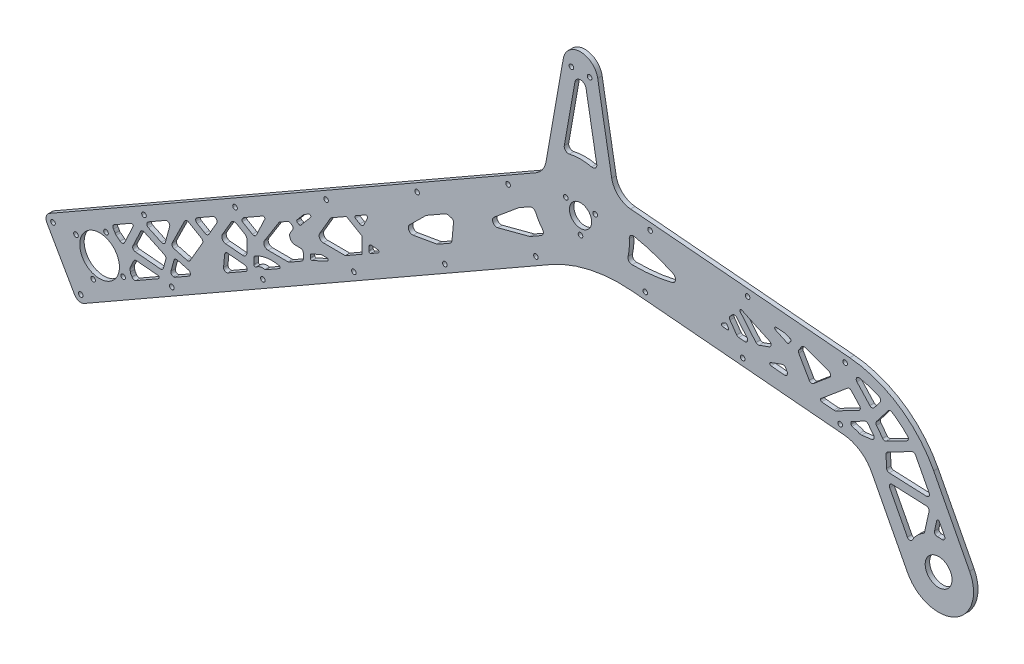
SolidWorks part; units mm, degrees
material "6061-T6 (SS)"
ref_plane "Front Plane" through (0, 0, 0) normal (0, 0, 1) x (1, 0, 0)
ref_plane "Top Plane" through (0, 0, 0) normal (0, 1, 0) x (1, 0, 0)
ref_plane "Right Plane" through (0, 0, 0) normal (1, 0, 0) x (0, 0, -1)
sketch "Reference Sketch" plane through (0, 0, 0) normal (0, 0, 1) x (1, 0, 0)
  line L0 (-343.92, -196.825) -> (0, 0) construction
  line L1 (-243.92, 103.175) -> (356.08, 103.175) construction
  line L2 (-243.92, 103.175) -> (-243.92, 0) construction
  line L3 (-243.92, 0) -> (356.08, 0) construction
  line L4 (356.08, 103.175) -> (356.08, 0) construction
  line L5 (0, 0) -> (256.08, -92.7116) construction
  line L6 (256.08, -92.7116) -> (56.08, -196.825) construction
  line L7 (256.08, -92.7116) -> (456.08, -196.825) construction
  line L8 (-343.92, -196.825) -> (56.08, -196.825) construction
  line L9 (56.08, -196.825) -> (456.08, -196.825) construction
  circle A1 centre (-343.92, -196.825) radius 100 construction
  circle A2 centre (56.08, -196.825) radius 100 construction
  circle A3 centre (456.08, -196.825) radius 100 construction
  circle A4 centre (-343.92, -196.825) radius 16.05 construction
  circle A5 centre (-343.92, -196.825) radius 28.55 construction
  circle A6 centre (-343.92, -196.825) radius 38.55 construction
  circle A7 centre (-343.92, -196.825) radius 33.55 construction
  point P13 (-343.92, -296.825)
  point P14 (556.08, -196.825)
  point P17 (-443.92, -196.825)
  dimension "D3" = 32.1
  dimension "D5" = 200
  dimension "D9" = 57.1
  dimension "D10" = 10
  dimension "D11" = 5
  dimension "D1" = 600
  dimension "D2" = 103.175
  dimension "D4" = 243.92
  dimension "D6" = 125
  dimension "D7" = 400
  dimension "D8" = 1000
  dimension "D12" = 356.08
sketch "Sketch2" plane through (0, 0, 0) normal (0, 0, 1) x (1, 0, 0)
  line L0 (-379.7168, -188.5069) -> (-32.0065, 10.4873)
  line L1 (-354.8814, -231.9028) -> (-21.5627, -41.1449)
  line L2 (-343.92, -196.825) -> (0, 0) construction
  line L3 (-184.3777, -76.7146) -> (-159.5423, -120.1104) construction
  line L4 (-24.685, 20.9013) -> (-12.3101, 91.0831)
  line L5 (12.3101, 91.0831) -> (22.322, 34.3028)
  line L6 (0, 98.4125) -> (0, 112.7) construction
  line L7 (-5.4848, 79.4125) -> (5.4848, 79.4125) construction
  line L8 (5.4848, 79.4125) -> (10.9697, 88.9125) construction
  line L9 (10.9697, 88.9125) -> (5.4848, 98.4125) construction
  line L10 (5.4848, 98.4125) -> (-5.4848, 98.4125) construction
  line L11 (-5.4848, 98.4125) -> (-10.9697, 88.9125) construction
  line L12 (-10.9697, 88.9125) -> (-5.4848, 79.4125) construction
  line L13 (-243.92, 103.175) -> (356.08, 103.175) construction
  line L14 (0, 88.9125) -> (0, 0) construction
  line L15 (35.7868, 21.9646) -> (192.5861, 8.2464)
  line L16 (252.5753, -31.8371) -> (278.2553, -81.1679)
  line L17 (233.9047, -104.2553) -> (208.2247, -54.9245)
  line L18 (36.8237, -28.3172) -> (188.2284, -41.5633)
  line L19 (0, 0) -> (192.5861, -16.8491) construction
  line L21 (-360.8064, -192.2315) -> (-339.3265, -179.9386) construction
  line L22 (-381.5729, -195.33) -> (-361.7045, -230.0467)
  line L23 (256.08, -92.7116) -> (56.08, -196.825) construction
  line L25 (-243.92, 0) -> (356.08, 0) construction
  circle A0 centre (0, 0) radius 7.9375
  circle A1 centre (-343.92, -196.825) radius 14.2
  arc A3 (-12.3101, 91.0831) -> (12.3101, 91.0831) centre (0, 88.9125) cw
  circle A4 centre (0, 88.9125) radius 6.5 construction
  circle A5 centre (-6.5, 88.9125) radius 1.65
  circle A6 centre (6.5, 88.9125) radius 1.65
  circle A7 centre (0, 88.9125) radius 9.5 construction
  arc A8 (252.5753, -31.8371) -> (192.5861, 8.2464) centre (186.0495, -66.4682) ccw
  circle A9 centre (256.08, -92.7116) radius 9.5885
  arc A10 (278.2553, -81.1679) -> (233.9047, -104.2553) centre (256.08, -92.7116) cw
  arc A11 (-21.5627, -41.1449) -> (36.8237, -28.3172) centre (28.1082, -127.9366) cw
  arc A12 (188.2284, -41.5633) -> (208.2247, -54.9245) centre (186.0495, -66.4682) cw
  arc A13 (22.322, 34.3028) -> (35.7868, 21.9646) centre (37.0941, 36.9075) ccw
  arc A14 (-32.0065, 10.4873) -> (-24.685, 20.9013) centre (-39.4572, 23.506) ccw
  circle A17 centre (-343.92, -196.825) radius 17.5 construction
  circle A18 centre (-360.8064, -192.2315) radius 1.65
  circle A19 centre (-339.3265, -179.9386) radius 1.65
  circle A20 centre (-327.0336, -201.4185) radius 1.65
  circle A21 centre (-348.5135, -213.7114) radius 1.65
  arc A27 (-379.7168, -188.5069) -> (-381.5729, -195.33) centre (-377.2333, -192.8465) ccw
  arc A28 (-361.7045, -230.0467) -> (-354.8814, -231.9028) centre (-357.3649, -227.5632) ccw
  circle A29 centre (-343.92, -196.825) radius 33.55 construction
  circle A32 centre (-343.92, -196.825) radius 38.55 construction
  point P16 (-171.96, -98.4125)
  point P64 (-343.92, -196.825)
  dimension "D1" = 15.875
  dimension "D2" = 28.4
  dimension "D3" = 35
  dimension "D5" = 13
  dimension "D6" = 3.3
  dimension "D7" = 6
  dimension "D12" = 50
  dimension "D14" = 100
  dimension "D16" = 15
  dimension "D17" = 5
  dimension "D18" = 25
  dimension "D19" = 3.3
  dimension "D15" = 4
  dimension "D20" = 19.177
  dimension "D4" = 50
  dimension "D8" = 19
  dimension "D9" = 14.2875
  dimension "D10" = 9.525
  dimension "D11" = 10
  dimension "D13" = 50
extrude "Base" add sketch "Sketch2" along normal blind 3.175
sketch "Sketch3" plane through (0, 0, 3.175) normal (0, 0, 1) x (1, 0, 0)
  line L0 (-343.92, -196.825) -> (0, 0) construction
  line L5 (0, 0) -> (197.3986, -17.2701) construction
  line L6 (192.5861, 8.2464) -> (35.7868, 21.9646) construction
  line L9 (36.8237, -28.3172) -> (188.2284, -41.5633) construction
  line L10 (-31.8958, -41.2976) -> (0, 0) construction
  line L11 (0, 0) -> (46.2693, -24.1244) construction
  circle A0 centre (-357.3649, -227.5632) radius 1.65
  circle A1 centre (-343.92, -196.825) radius 33.55 construction
  arc A2 (-361.7045, -230.0467) -> (-354.8814, -231.9028) centre (-357.3649, -227.5632) ccw construction
  circle A3 centre (-292.2711, -190.3101) radius 1.65
  circle A4 centre (-227.1773, -153.057) radius 1.65
  circle A5 centre (-162.0835, -115.8038) radius 1.65
  circle A6 centre (-96.9897, -78.5507) radius 1.65
  circle A7 centre (-31.8958, -41.2976) radius 1.65
  circle A8 centre (-312.1394, -155.5934) radius 1.65
  circle A9 centre (-377.2333, -192.8465) radius 1.65
  circle A10 centre (-247.0456, -118.3403) radius 1.65
  circle A11 centre (-181.9518, -81.0871) radius 1.65
  circle A12 centre (-116.858, -43.834) radius 1.65
  circle A13 centre (-51.7642, -6.5809) radius 1.65
  circle A14 centre (46.2693, -24.1244) radius 1.65
  circle A15 centre (116.0029, -30.2253) radius 1.65
  circle A16 centre (185.7366, -36.3262) radius 1.65
  circle A17 centre (189.2228, 3.5215) radius 1.65
  circle A18 centre (119.4892, 9.6224) radius 1.65
  circle A19 centre (49.7555, 15.7234) radius 1.65
  dimension "D1" = 3.3
  dimension "D2" = 6
  dimension "D3" = 5
  dimension "D5" = 3
  dimension "D4" = 75
  dimension "D6" = 70
extrude "Strut Holes" cut sketch "Sketch3" against normal through all
sketch "Sketch6" plane through (0, 0, 3.175) normal (0, 0, 1) x (1, 0, 0)
  line L0 (-317.9371, -199.2378) -> (-301.7593, -189.9792)
  line L1 (-354.8814, -231.9028) -> (-21.5627, -41.1449) construction
  line L2 (-289.845, -183.1607) -> (-279.9388, -177.4914)
  line L3 (-225.0683, -146.089) -> (-215.3943, -140.5526)
  line L4 (-202.4502, -105.5293) -> (-201.3111, -106.1928)
  line L5 (-333.4446, -172.395) -> (-321.3247, -165.4588)
  line L6 (-32.0065, 10.4873) -> (-379.7168, -188.5069) construction
  line L7 (-319.9233, -166.7528) -> (-326.0767, -179.819)
  line L8 (-329.2222, -183.6702) -> (-327.9453, -183.7868) construction
  line L9 (-302.165, -188.1154) -> (-317.5291, -186.7124)
  line L10 (-319.5204, -187.852) -> (-321.9207, -192.9489)
  line L11 (-296.5261, -175.2812) -> (-298.2962, -181.7883)
  line L12 (-300.4079, -183.2551) -> (-318.4265, -181.6097)
  line L13 (-320.054, -178.7659) -> (-314.5879, -167.159)
  line L14 (-311.9264, -166.2018) -> (-297.6038, -172.9468)
  line L15 (-280.4073, -173.8257) -> (-288.2923, -171.6808)
  line L16 (-290.7472, -173.0857) -> (-292.8686, -180.8843)
  line L17 (-296.7252, -151.3805) -> (-309.1621, -158.4982)
  line L18 (-309.0208, -162.0434) -> (-299.7125, -166.427)
  line L19 (-296.9305, -165.1426) -> (-293.8019, -153.6413)
  line L20 (-290.7492, -165.8308) -> (-281.4187, -168.3689)
  line L21 (-279.1655, -167.4456) -> (-270.335, -152.2839)
  line L22 (-271.0566, -149.5491) -> (-280.339, -144.1428)
  line L23 (-283.1398, -144.9875) -> (-292.0185, -163.0173)
  line L24 (-274.1749, -138.475) -> (-262.8296, -131.9821)
  line L25 (-260.108, -134.7245) -> (-265.8054, -144.5068)
  line L26 (-268.5402, -145.2285) -> (-274.188, -141.9391)
  line L27 (-255.2613, -159.7424) -> (-254.4886, -151.2802)
  line L28 (-252.315, -149.4703) -> (-240.2297, -150.5739)
  line L29 (-292.2711, -190.3101) -> (-299.0066, -188.4038) construction
  line L30 (-252.2762, -161.6601) -> (-239.4181, -154.3014)
  line L31 (-249.9491, -129.2039) -> (-256.1296, -139.8156)
  line L32 (-253.8101, -144.313) -> (-241.8428, -145.4058)
  line L33 (-238.5701, -142.4296) -> (-238.5385, -134.1139)
  line L34 (-240.0286, -131.5101) -> (-245.8469, -128.1214)
  line L35 (-233.5719, -142.9305) -> (-233.588, -147.1604)
  line L36 (-241.7536, -124.7193) -> (-234.6398, -128.8625)
  line L37 (-231.8238, -127.9864) -> (-225.7969, -115.1887)
  line L38 (-227.1983, -113.8948) -> (-240.4869, -121.4998)
  line L39 (-215.7001, -112.1928) -> (-226.033, -128.59)
  line L40 (-223.5063, -133.1894) -> (-209.2023, -133.2437)
  line L41 (-208.2012, -132.9795) -> (-199.2535, -127.8588)
  line L42 (-198.247, -126.1305) -> (-198.2324, -122.2852)
  line L43 (-200.2248, -120.2776) -> (-204.0086, -120.2632)
  line L44 (-207.3776, -114.1307) -> (-205.8611, -111.7242)
  line L45 (-206.5466, -108.9297) -> (-207.4931, -108.3784)
  line L46 (-209.4931, -108.3708) -> (-215.0015, -111.5233)
  line L47 (-220.5938, -138.2005) -> (-191.3457, -138.3115) construction
  line L48 (-200.0442, -105.9743) -> (-193.1087, -97.7724)
  line L49 (-194.3691, -96.2588) -> (-197.5103, -98.0565)
  line L50 (-198.0441, -98.501) -> (-202.7105, -104.0195)
  line L51 (-193.2277, -121.0545) -> (-193.2345, -122.8478)
  line L52 (-191.8153, -123.7595) -> (-180.9934, -118.7631)
  line L54 (-192.6468, -120.1504) -> (-185.8787, -117.0256)
  line L55 (-185.0328, -116.8414) -> (-181.4088, -116.8552)
  line L56 (-168.149, -108.9055) -> (-183.9527, -108.8455)
  line L57 (-186.5337, -104.3356) -> (-178.5799, -90.6792)
  line L58 (-178.5799, -90.6792) -> (-167.3868, -84.2735)
  line L59 (-167.3868, -84.2735) -> (-156.3884, -90.6792)
  line L60 (-156.3884, -90.6792) -> (-156.4321, -102.1999)
  line L61 (-156.4321, -102.1999) -> (-168.149, -108.9055)
  line L62 (-178.5799, -90.6792) -> (-168.149, -108.9055) construction
  line L63 (-151.4146, -97.6001) -> (-151.4054, -95.1814)
  line L64 (-149.2236, -93.1973) -> (-145.0326, -93.58)
  line L65 (-144.6268, -95.4437) -> (-149.9179, -98.4719)
  line L66 (-160.8726, -80.5454) -> (-153.7619, -76.4759)
  line L67 (-152.3605, -77.7699) -> (-154.93, -83.2262)
  line L68 (-157.746, -84.1023) -> (-160.8792, -82.2774)
  line L69 (-155.8599, -85.2008) -> (-151.3971, -92.9988) construction
  line L70 (-90.8199, -49.6985) -> (-91.8964, -61.4879)
  line L71 (-93.3939, -63.8188) -> (-101.9943, -68.7409)
  line L72 (-102.9747, -69.0935) -> (-119.6299, -71.9651)
  line L73 (-122.2529, -66.8794) -> (-110.6811, -55.3952)
  line L74 (-110.058, -54.9208) -> (-96.7247, -47.2901)
  line L75 (-94.4471, -46.9991) -> (-92.2866, -47.5868)
  line L76 (-102.4534, -69.0036) -> (-110.4008, -55.117) construction
  line L78 (-28.0968, -26.4494) -> (-35.8254, -30.8725)
  line L79 (-36.5501, -31.1694) -> (-59.134, -37.129)
  line L80 (-61.819, -31.9228) -> (-44.3172, -17.3499)
  line L81 (-43.8877, -17.0516) -> (-36.2746, -12.6946)
  line L82 (-44.1155, -17.182) -> (-36.1682, -31.0687) construction
  line L83 (-11.5997, 37.5245) -> (-3.9861, 80.7029)
  line L84 (3.9861, 80.7029) -> (11.5997, 37.5245)
  line L85 (22.322, 34.3028) -> (12.3101, 91.0831) construction
  line L86 (-12.3101, 91.0831) -> (-24.685, 20.9013) construction
  line L87 (192.5861, 8.2464) -> (35.7868, 21.9646) construction
  line L88 (36.8237, -28.3172) -> (188.2284, -41.5633) construction
  line L89 (-227.1773, -153.057) -> (-233.9128, -151.1507) construction
  line L90 (246.076, -72.9136) -> (249.254, -58.5784)
  line L91 (247.3887, -56.1475) -> (222.9622, -55.081)
  line L92 (221.1009, -58.0026) -> (233.7353, -82.273)
  line L93 (208.2247, -54.9245) -> (233.9047, -104.2553) construction
  line L94 (253.1337, -68.7997) -> (254.752, -61.5)
  line L95 (256.6153, -61.2547) -> (260.3456, -68.4206)
  line L96 (278.2553, -81.1679) -> (252.5753, -31.8371) construction
  line L97 (249.3108, -47.2228) -> (239.5975, -28.5637)
  line L98 (236.9, -27.7132) -> (219.5656, -36.7369)
  line L99 (218.491, -38.5982) -> (218.8608, -47.0688)
  line L100 (220.7717, -48.9796) -> (247.4495, -50.1444)
  line L101 (233.4135, -22.7639) -> (218.6181, -30.4658)
  line L102 (216.1079, -29.9093) -> (211.6718, -24.1281)
  line L103 (211.6718, -21.693) -> (220.0072, -10.8302)
  line L104 (209.6166, -31.3057) -> (205.7463, -26.2618)
  line L105 (203.2361, -25.7053) -> (194.0101, -30.5081)
  line L106 (193.4718, -31.3951) -> (193.4718, -32.4967)
  line L107 (201.069, -35.4569) -> (208.2909, -34.5061)
  line L108 (214.3031, -8.4078) -> (209.9577, -14.0708)
  line L109 (197.6887, -4.156) -> (206.8964, -14.2045)
  line L110 (193.6814, -11.6243) -> (199.5455, -18.0239)
  line L111 (198.9945, -21.1491) -> (182.8075, -29.5754)
  line L112 (181.1608, -29.903) -> (172.4826, -29.1438)
  line L113 (171.927, -27.3815) -> (190.9213, -11.4434)
  line L114 (178.1992, -11.0225) -> (166.5918, -20.7623)
  line L115 (163.5742, -20.2302) -> (156.048, -7.1944)
  line L116 (156.1417, -5.0472) -> (158.1885, -2.1242)
  line L117 (160.5108, -1.3919) -> (177.5977, -7.611)
  line L118 (146.6448, -20.9077) -> (147.747, -22.8167)
  line L119 (145.8406, -25.8091) -> (136.23, -24.9682)
  line L120 (135.9751, -23.0324) -> (144.2287, -20.0283)
  line L121 (134.9743, -13.819) -> (127.6718, -16.4769)
  line L122 (125.4557, -15.8831) -> (114.1985, -2.4673)
  line L123 (115.3872, -0.9182) -> (135.1355, -10.127)
  line L124 (139.4306, -1.096) -> (147.8318, -5.0136)
  line L125 (149.0736, -4.6809) -> (150.4259, -2.7496)
  line L126 (149.9488, -1.2363) -> (146.0985, 0.1651)
  line L127 (145.3339, 0.3346) -> (139.9404, 0.8065)
  line L128 (111.6605, -7.2212) -> (119.0455, -16.0223)
  line L129 (117.3391, -19.3002) -> (113.1162, -18.9308)
  line L130 (111.6522, -18.0855) -> (106.8775, -11.2665)
  line L131 (107.1016, -8.7052) -> (108.7142, -7.0926)
  line L132 (104.7039, -15.1361) -> (105.7554, -16.6377)
  line L133 (104.8491, -18.2075) -> (101.6773, -17.93)
  line L134 (101.2644, -16.0678) -> (103.3847, -14.8436)
  arc A0 (-320.7312, -198.3723) -> (-321.5152, -197.1118) centre (-327.0336, -201.4185) ccw
  arc A1 (-291.1568, -183.3993) -> (-291.2348, -183.3872) centre (-292.2711, -190.3101) ccw
  arc A2 (-225.7665, -146.2006) -> (-231.9116, -147.9008) centre (-227.1773, -153.057) ccw
  arc A4 (-321.937, -195.96) -> (-322.0953, -194.053) centre (-343.92, -196.825) ccw
  arc A5 (-332.8179, -177.3623) -> (-333.9791, -175.4215) centre (-339.3265, -179.9386) ccw
  arc A6 (-329.2222, -180.455) -> (-332.0384, -178.3094) centre (-343.92, -196.825) ccw
  arc A8 (-232.5183, -141.1762) -> (-215.6911, -138.7049) centre (-220.6887, -163.2003) cw
  arc A9 (-241.9747, -123.1658) -> (-241.1717, -122.1478) centre (-247.0456, -118.3403) ccw
  arc A10 (-32.0383, -14.0906) -> (-27.2511, -21.9631) centre (0, 0) ccw
  arc A11 (-256.1296, -139.8156) -> (-253.8101, -144.313) centre (-253.5373, -141.3254) ccw
  arc A12 (-226.033, -128.59) -> (-223.5063, -133.1894) centre (-223.4949, -130.1894) ccw
  arc A13 (-183.9527, -108.8455) -> (-186.5337, -104.3356) centre (-183.9413, -105.8455) cw
  arc A14 (-119.6299, -71.9651) -> (-122.2529, -66.8794) centre (-120.1396, -69.0087) cw
  arc A15 (-59.134, -37.129) -> (-61.819, -31.9228) centre (-59.8994, -34.2283) cw
  arc A16 (-7.9627, 34.0822) -> (7.9627, 34.0822) centre (0, 0) cw
  arc A17 (-3.9861, 80.7029) -> (3.9861, 80.7029) centre (0, 80) cw
  arc A18 (34.8636, 3.0867) -> (34.0029, -8.2948) centre (0, 0) cw
  arc A19 (38.4335, 6.2944) -> (66.0977, -2.7713) centre (15.1723, -111.4295) cw
  arc A20 (66.0977, -2.7713) -> (65.4856, -8.7407) centre (64.749, -5.6491) cw
  arc A21 (36.898, -12.0057) -> (65.4856, -8.7407) centre (37.6733, 107.9918) ccw
  arc A22 (245.141, -74.2025) -> (237.26, -82.3165) centre (256.08, -92.7116) ccw
  arc A23 (258.3595, -71.3328) -> (255.1708, -71.2308) centre (256.08, -92.7116) ccw
  arc A24 (222.6875, -10.3732) -> (233.9189, -19.5905) centre (186.0495, -66.4682) cw
  arc A25 (252.5753, -31.8371) -> (192.5861, 8.2464) centre (186.0495, -66.4682) ccw construction
  arc A26 (194.2312, -33.4673) -> (199.4914, -35.2382) centre (186.0495, -66.4682) cw
  arc A27 (208.2247, -54.9245) -> (188.2284, -41.5633) centre (186.0495, -66.4682) ccw construction
  arc A28 (213.5369, -5.3663) -> (199.5667, -0.8459) centre (186.0495, -66.4682) ccw
  arc A29 (218.8608, -47.0688) -> (220.7717, -48.9796) centre (220.8589, -46.9815) ccw
  arc A30 (239.5975, -28.5637) -> (236.9, -27.7132) centre (237.8235, -29.4872) ccw
  arc A31 (219.5656, -36.7369) -> (218.491, -38.5982) centre (220.4891, -38.5109) ccw
  arc A32 (127.6718, -16.4769) -> (125.4557, -15.8831) centre (126.9878, -14.5975) cw
  arc A33 (-240.4869, -121.4998) -> (-241.1717, -122.1478) centre (-239.4934, -123.2356) ccw
  arc A34 (-234.6398, -128.8625) -> (-231.8238, -127.9864) centre (-233.6332, -127.1343) ccw
  arc A35 (-233.5719, -142.9305) -> (-232.5183, -141.1762) centre (-231.5719, -142.9381) cw
  arc A36 (-317.9371, -199.2378) -> (-320.7312, -198.3723) centre (-318.9305, -197.5019) cw
  arc A37 (-321.937, -195.96) -> (-321.5152, -197.1118) centre (-319.9386, -195.8813) ccw
  arc A38 (-321.9207, -192.9489) -> (-322.0953, -194.053) centre (-320.1113, -193.801) ccw
  arc A39 (-317.5291, -186.7124) -> (-319.5204, -187.852) centre (-317.711, -188.7042) ccw
  arc A42 (-332.8179, -177.3623) -> (-332.0384, -178.3094) centre (-330.9583, -176.6261) ccw
  arc A43 (-333.4446, -172.395) -> (-333.9791, -175.4215) centre (-332.4512, -174.1309) ccw
  arc A44 (-318.4265, -181.6097) -> (-320.054, -178.7659) centre (-318.2446, -179.618) cw
  arc A45 (-298.2962, -181.7883) -> (-300.4079, -183.2551) centre (-300.226, -181.2634) cw
  arc A46 (-289.845, -183.1607) -> (-291.1568, -183.3993) centre (-290.8384, -181.4248) cw
  arc A47 (-292.8686, -180.8843) -> (-291.2348, -183.3872) centre (-290.9387, -181.4092) ccw
  arc A48 (-280.4073, -173.8257) -> (-279.9388, -177.4914) centre (-280.9322, -175.7556) cw
  arc A49 (-288.2923, -171.6808) -> (-290.7472, -173.0857) centre (-288.8173, -173.6107) ccw
  arc A50 (-296.5261, -175.2812) -> (-297.6038, -172.9468) centre (-298.456, -174.7562) ccw
  arc A51 (-314.5879, -167.159) -> (-311.9264, -166.2018) centre (-312.7785, -168.0112) cw
  arc A52 (-309.1621, -158.4982) -> (-309.0208, -162.0434) centre (-308.1687, -160.234) ccw
  arc A53 (-296.7252, -151.3805) -> (-293.8019, -153.6413) centre (-295.7318, -153.1164) cw
  arc A54 (-299.7125, -166.427) -> (-296.9305, -165.1426) centre (-298.8604, -164.6177) ccw
  arc A55 (-290.7492, -165.8308) -> (-292.0185, -163.0173) centre (-290.2242, -163.9009) cw
  arc A56 (-281.4187, -168.3689) -> (-279.1655, -167.4456) centre (-280.8937, -166.439) ccw
  arc A57 (-270.335, -152.2839) -> (-271.0566, -149.5491) centre (-272.0632, -151.2774) ccw
  arc A58 (-280.339, -144.1428) -> (-283.1398, -144.9875) centre (-281.3456, -145.8711) ccw
  arc A59 (-274.1749, -138.475) -> (-274.188, -141.9391) centre (-273.1814, -140.2108) ccw
  arc A60 (-265.8054, -144.5068) -> (-268.5402, -145.2285) centre (-267.5336, -143.5003) cw
  arc A61 (-254.4886, -151.2802) -> (-252.315, -149.4703) centre (-252.4969, -151.462) cw
  arc A62 (-255.2613, -159.7424) -> (-252.2762, -161.6601) centre (-253.2696, -159.9243) ccw
  arc A63 (-239.4181, -154.3014) -> (-240.2297, -150.5739) centre (-240.4115, -152.5656) ccw
  arc A64 (-262.8296, -131.9821) -> (-260.108, -134.7245) centre (-261.8362, -133.718) cw
  arc A65 (-209.2023, -133.2437) -> (-208.2012, -132.9795) centre (-209.1947, -131.2437) ccw
  arc A66 (-215.0015, -111.5233) -> (-215.7001, -112.1928) centre (-214.0081, -113.2591) ccw
  arc A67 (-207.4931, -108.3784) -> (-209.4931, -108.3708) centre (-208.4997, -110.1067) ccw
  arc A68 (-205.8611, -111.7242) -> (-206.5466, -108.9297) centre (-207.5531, -110.658) ccw
  arc A69 (-204.0086, -120.2632) -> (-207.3776, -114.1307) centre (-203.9934, -116.2633) cw
  arc A70 (-198.2324, -122.2852) -> (-200.2248, -120.2776) centre (-200.2323, -122.2776) ccw
  arc A71 (-199.2535, -127.8588) -> (-198.247, -126.1305) centre (-200.2469, -126.1229) ccw
  arc A72 (-185.8787, -117.0256) -> (-185.0328, -116.8414) centre (-185.0404, -118.8414) cw
  arc A73 (-197.5103, -98.0565) -> (-198.0441, -98.501) centre (-196.5169, -99.7924) ccw
  arc A74 (-151.4054, -95.1814) -> (-149.2236, -93.1973) centre (-149.4054, -95.189) cw
  arc A75 (-154.93, -83.2262) -> (-157.746, -84.1023) centre (-156.7394, -82.374) cw
  arc A76 (-90.8199, -49.6985) -> (-92.2866, -47.5868) centre (-92.8116, -49.5167) ccw
  arc A77 (111.6605, -7.2212) -> (108.7142, -7.0926) centre (110.1284, -8.5068) ccw
  arc A78 (106.8775, -11.2665) -> (107.1016, -8.7052) centre (108.5158, -10.1194) cw
  arc A79 (113.1162, -18.9308) -> (111.6522, -18.0855) centre (113.2905, -16.9384) cw
  arc A80 (119.0455, -16.0223) -> (117.3391, -19.3002) centre (117.5134, -17.3078) cw
  arc A81 (134.9743, -13.819) -> (135.1355, -10.127) centre (134.2903, -11.9396) ccw
  arc A82 (146.6448, -20.9077) -> (144.2287, -20.0283) centre (144.9128, -21.9077) ccw
  arc A83 (147.747, -22.8167) -> (145.8406, -25.8091) centre (146.0149, -23.8167) cw
  arc A84 (156.048, -7.1944) -> (156.1417, -5.0472) centre (157.78, -6.1944) cw
  arc A85 (158.1885, -2.1242) -> (160.5108, -1.3919) centre (159.8268, -3.2713) cw
  arc A86 (178.1992, -11.0225) -> (177.5977, -7.611) centre (176.9136, -9.4904) ccw
  arc A87 (166.5918, -20.7623) -> (163.5742, -20.2302) centre (165.3062, -19.2302) cw
  arc A88 (193.6814, -11.6243) -> (190.9213, -11.4434) centre (192.2068, -12.9755) ccw
  arc A89 (199.5455, -18.0239) -> (198.9945, -21.1491) centre (198.071, -19.375) cw
  arc A90 (209.9577, -14.0708) -> (206.8964, -14.2045) centre (208.371, -12.8533) cw
  arc A91 (213.5369, -5.3663) -> (214.3031, -8.4078) centre (212.7164, -7.1903) cw
  arc A92 (233.9189, -19.5905) -> (233.4135, -22.7639) centre (232.49, -20.9899) cw
  arc A93 (222.6875, -10.3732) -> (220.0072, -10.8302) centre (221.5939, -12.0477) ccw
  arc A94 (211.6718, -24.1281) -> (211.6718, -21.693) centre (213.2585, -22.9105) cw
  arc A95 (218.6181, -30.4658) -> (216.1079, -29.9093) centre (217.6946, -28.6918) cw
  arc A96 (205.7463, -26.2618) -> (203.2361, -25.7053) centre (204.1595, -27.4793) ccw
  arc A97 (209.6166, -31.3057) -> (208.2909, -34.5061) centre (208.0299, -32.5232) cw
  arc A98 (246.076, -72.9136) -> (245.141, -74.2025) centre (244.1234, -72.4807) cw
  arc A99 (249.254, -58.5784) -> (247.3887, -56.1475) centre (247.3014, -58.1456) ccw
  arc A100 (222.9622, -55.081) -> (221.1009, -58.0026) centre (222.8749, -57.0791) ccw
  arc A101 (233.7353, -82.273) -> (237.26, -82.3165) centre (235.5093, -81.3495) ccw
  arc A102 (260.3456, -68.4206) -> (258.3595, -71.3328) centre (258.5716, -69.344) cw
  arc A103 (253.1337, -68.7997) -> (255.1708, -71.2308) centre (255.0863, -69.2326) ccw
  arc A104 (249.3108, -47.2228) -> (247.4495, -50.1444) centre (247.5367, -48.1463) cw
  arc A105 (199.5667, -0.8459) -> (197.6887, -4.156) centre (199.1632, -2.8048) ccw
  arc A106 (-215.6911, -138.7049) -> (-215.3943, -140.5526) centre (-215.891, -139.6847) cw
  arc A107 (-301.7593, -189.9792) -> (-302.165, -188.1154) centre (-302.256, -189.1113) ccw
  arc A108 (-321.3247, -165.4588) -> (-319.9233, -166.7528) centre (-320.828, -166.3267) cw
  arc A109 (-225.7969, -115.1887) -> (-227.1983, -113.8948) centre (-226.7016, -114.7627) ccw
  arc A110 (-241.7536, -124.7193) -> (-241.9747, -123.1658) centre (-241.2503, -123.8551) cw
  arc A111 (-225.7665, -146.2006) -> (-225.0683, -146.089) centre (-225.565, -145.2211) ccw
  arc A112 (-233.588, -147.1604) -> (-231.9116, -147.9008) centre (-232.588, -147.1642) ccw
  arc A113 (-202.4502, -105.5293) -> (-202.7105, -104.0195) centre (-201.9469, -104.6652) cw
  arc A114 (-201.3111, -106.1928) -> (-200.0442, -105.9743) centre (-200.8078, -105.3286) ccw
  arc A115 (-193.2277, -121.0545) -> (-192.6468, -120.1504) centre (-192.2277, -121.0583) cw
  arc A116 (-193.2345, -122.8478) -> (-191.8153, -123.7595) centre (-192.2345, -122.8516) ccw
  arc A117 (-193.1087, -97.7724) -> (-194.3691, -96.2588) centre (-193.8723, -97.1267) ccw
  arc A118 (-180.9934, -118.7631) -> (-181.4088, -116.8552) centre (-181.4126, -117.8552) ccw
  arc A119 (-153.7619, -76.4759) -> (-152.3605, -77.7699) centre (-153.2652, -77.3438) cw
  arc A120 (-160.8726, -80.5454) -> (-160.8792, -82.2774) centre (-160.3759, -81.4133) ccw
  arc A121 (-151.4146, -97.6001) -> (-149.9179, -98.4719) centre (-150.4146, -97.6039) ccw
  arc A122 (-145.0326, -93.58) -> (-144.6268, -95.4437) centre (-145.1235, -94.5758) cw
  arc A123 (101.6773, -17.93) -> (101.2644, -16.0678) centre (101.7644, -16.9338) cw
  arc A124 (104.7039, -15.1361) -> (103.3847, -14.8436) centre (103.8847, -15.7096) ccw
  arc A125 (105.7554, -16.6377) -> (104.8491, -18.2075) centre (104.9362, -17.2113) cw
  arc A126 (114.1985, -2.4673) -> (115.3872, -0.9182) centre (114.9646, -1.8245) cw
  arc A127 (136.23, -24.9682) -> (135.9751, -23.0324) centre (136.3171, -23.972) cw
  arc A128 (139.4306, -1.096) -> (139.9404, 0.8065) centre (139.8532, -0.1897) cw
  arc A129 (172.4826, -29.1438) -> (171.927, -27.3815) centre (172.5698, -28.1476) cw
  arc A130 (194.0101, -30.5081) -> (193.4718, -31.3951) centre (194.4718, -31.3951) ccw
  arc A131 (193.4718, -32.4967) -> (194.2312, -33.4673) centre (194.4718, -32.4967) ccw
  arc A132 (254.752, -61.5) -> (256.6153, -61.2547) centre (255.7283, -61.7164) cw
  arc A133 (146.0985, 0.1651) -> (145.3339, 0.3346) centre (145.0724, -2.654) ccw
  arc A134 (199.4914, -35.2382) -> (201.069, -35.4569) centre (200.6774, -32.4826) ccw
  arc A135 (182.8075, -29.5754) -> (181.1608, -29.903) centre (181.4223, -26.9144) cw
  arc A136 (-7.9627, 34.0822) -> (-11.5997, 37.5245) centre (-8.6452, 37.0035) cw
  arc A137 (7.9627, 34.0822) -> (11.5997, 37.5245) centre (8.6452, 37.0035) ccw
  arc A138 (34.8636, 3.0867) -> (38.4335, 6.2944) centre (37.8519, 3.3513) cw
  arc A139 (34.0029, -8.2948) -> (36.898, -12.0057) centre (36.9174, -9.0058) ccw
  arc A140 (-35.8254, -30.8725) -> (-36.5501, -31.1694) centre (-37.3155, -28.2687) cw
  arc A141 (-44.3172, -17.3499) -> (-43.8877, -17.0516) centre (-42.3976, -19.6554) cw
  arc A142 (-32.0383, -14.0906) -> (-36.2746, -12.6946) centre (-34.7845, -15.2984) ccw
  arc A143 (-27.2511, -21.9631) -> (-28.0968, -26.4494) centre (-29.5869, -23.8456) cw
  arc A144 (-96.7247, -47.2901) -> (-94.4471, -46.9991) centre (-95.2346, -49.8939) cw
  arc A145 (-91.8964, -61.4879) -> (-93.3939, -63.8188) centre (-94.884, -61.2151) cw
  arc A146 (-110.6811, -55.3952) -> (-110.058, -54.9208) centre (-108.5679, -57.5245) cw
  arc A147 (-101.9943, -68.7409) -> (-102.9747, -69.0935) centre (-103.4845, -66.1371) cw
  arc A148 (-249.9491, -129.2039) -> (-245.8469, -128.1214) centre (-247.3568, -130.7138) cw
  arc A149 (-238.5385, -134.1139) -> (-240.0286, -131.5101) centre (-241.5385, -134.1025) ccw
  arc A150 (-241.8428, -145.4058) -> (-238.5701, -142.4296) centre (-241.57, -142.4182) ccw
  arc A151 (150.4259, -2.7496) -> (149.9488, -1.2363) centre (149.6067, -2.176) ccw
  arc A152 (147.8318, -5.0136) -> (149.0736, -4.6809) centre (148.2544, -4.1073) ccw
  arc A153 (-329.2222, -180.455) -> (-326.0767, -179.819) centre (-327.8861, -178.9669) ccw
  point P98 (-116.858, -43.834)
  point P110 (-258.4996, -143.8848)
  point P113 (-228.9184, -133.1688)
  point P143 (34.9003, -2.6394)
  point P203 (218.9408, -48.8997)
  point P206 (238.674, -26.7897)
  point P211 (126.3559, -16.9559)
  point P214 (-240.9361, -121.7569)
  point P217 (-232.7537, -129.961)
  point P220 (-233.5675, -141.7728)
  point P229 (-318.9237, -186.5851)
  point P232 (-327.9453, -183.7868)
  point P234 (-327.9453, -183.7868)
  point P235 (-326.0754, -183.9575)
  point P240 (-335.9304, -173.8176)
  point P247 (-290.5028, -183.5371)
  point P252 (-275.7482, -175.0931)
  point P255 (-290.2222, -171.1558)
  point P262 (-312.4966, -160.4065)
  point P265 (-292.5345, -148.9822)
  point P268 (-297.5562, -167.4426)
  point P271 (-293.0903, -165.1939)
  point P278 (-282.1923, -143.0634)
  point P281 (-277.1814, -140.1957)
  point P288 (-255.6107, -163.5684)
  point P294 (-256.3514, -128.2747)
  point P297 (-208.6664, -133.2457)
  point P300 (-215.4343, -111.7709)
  point P303 (-208.4909, -107.7973)
  point P308 (-211.2248, -120.2358)
  point P311 (-198.2248, -120.2852)
  point P314 (-198.2513, -127.2852)
  point P329 (110.2575, -5.5492)
  point P334 (112.1872, -18.8495)
  point P337 (122.1491, -19.721)
  point P340 (139.5116, -12.1676)
  point P345 (149.6679, -26.1439)
  point P350 (159.0687, -0.8671)
  point P353 (180.8529, -8.7958)
  point P356 (164.7659, -22.2944)
  point P363 (208.5067, -15.9618)
  point P366 (215.8118, -6.4415)
  point P369 (235.7568, -21.544)
  point P374 (210.7376, -22.9105)
  point P377 (217.1296, -31.2407)
  point P380 (204.7246, -24.9304)
  point P383 (211.7254, -34.054)
  point P390 (219.5014, -54.9299)
  point P393 (235.6626, -85.9753)
  point P396 (262.2729, -72.1228)
  point P401 (250.9103, -50.2955)
  point P406 (-213.2581, -139.3301)
  point P412 (-318.5721, -163.8835)
  point P415 (-224.4456, -112.3194)
  point P420 (-225.4089, -146.284)
  point P423 (-233.5998, -150.2728)
  point P426 (-203.48, -104.9295)
  point P431 (-193.2252, -120.4175)
  point P434 (-193.2404, -124.4175)
  point P437 (-189.4469, -93.4418)
  point P440 (-176.8981, -116.8723)
  point P447 (-151.4212, -99.3322)
  point P450 (-141.8741, -93.8684)
  point P453 (98.5177, -17.6536)
  point P458 (106.9854, -18.3944)
  point P463 (131.7364, -24.5751)
  point P468 (170.0776, -28.9333)
  point P471 (193.4718, -30.7883)
  point P474 (193.4718, -33.2883)
  point P477 (255.3467, -58.8176)
  point P484 (182.0319, -29.9792)
  point P491 (34.2849, 7.0387)
  point P494 (32.91, -11.9136)
  point P505 (-24.8853, -24.6115)
  point P508 (-95.6462, -46.6729)
  point P511 (-92.0384, -63.0431)
  point P524 (-238.5825, -145.7035)
  point P527 (151.1734, -1.682)
  point P530 (148.5923, -5.3682)
  point P531 (-329.2222, -183.7868)
  dimension "D1" = 14
  dimension "D2" = 10
  dimension "D3" = 2
  dimension "D5" = 22
  dimension "D6" = 9
  dimension "D12" = 5
  dimension "D19" = 7
  dimension "D31" = 7
  dimension "D40" = 25
  dimension "D44" = 19
  dimension "D62" = 5
  dimension "D92" = 35
  dimension "D96" = 3
  dimension "D97" = 10
  dimension "D100" = 15
  dimension "D104" = 30
  dimension "D105" = 120
  dimension "D107" = 43
  dimension "D116" = 65
  dimension "D117" = 8
  dimension "D127" = 9
  dimension "D128" = 6
  dimension "D171" = 2
  dimension "D172" = 1
  dimension "D173" = 3
  dimension "D174" = 1
  dimension "D175" = 4
  dimension "D176" = 2
  dimension "D7" = 35
  dimension "D8" = 35
  dimension "D9" = 20
  dimension "D10" = 22
  dimension "D11" = 20
  dimension "D13" = 5
  dimension "D14" = 45
  dimension "D15" = 45
  dimension "D16" = 17
  dimension "D17" = 15
  dimension "D18" = 5
  dimension "D20" = 55
  dimension "D21" = 5
  dimension "D22" = 45
  dimension "D23" = 23
  dimension "D24" = 34
  dimension "D25" = 60
  dimension "D26" = 5
  dimension "D27" = 5
  dimension "D28" = 5
  dimension "D29" = 30
  dimension "D30" = 24
  dimension "D32" = 55
  dimension "D33" = 35
  dimension "D34" = 25
  dimension "D35" = 5
  dimension "D36" = 6
  dimension "D37" = 60
  dimension "D38" = 5
  dimension "D39" = 20
  dimension "D41" = 11
  dimension "D42" = 35
  dimension "D43" = 60
  dimension "D45" = 19.5
  dimension "D46" = 5
  dimension "D47" = 5
  dimension "D48" = 30
  dimension "D49" = 5
  dimension "D50" = 14
  dimension "D51" = 13
  dimension "D52" = 8.5
  dimension "D53" = 60
  dimension "D54" = 12
  dimension "D55" = 7
  dimension "D56" = 22
  dimension "D57" = 28
  dimension "D58" = 60
  dimension "D59" = 15
  dimension "D60" = 8
  dimension "D61" = 13
  dimension "D63" = 12
  dimension "D64" = 20
  dimension "D65" = 5
  dimension "D66" = 65
  dimension "D67" = 25
  dimension "2" = 18
  dimension "D68" = 8
  dimension "D69" = 4
  dimension "D70" = 14
  dimension "D71" = 15
  dimension "D72" = 13.5
  dimension "D73" = 60
  dimension "D74" = 60
  dimension "D75" = 8
  dimension "D76" = 5
  dimension "D77" = 35
  dimension "D78" = 0.5076
  dimension "D79" = 5
  dimension "D80" = 11
  dimension "D81" = 35
  dimension "D82" = 16
  dimension "D83" = 18
  dimension "D84" = 55
  dimension "D85" = 45
  dimension "D86" = 20
  dimension "D87" = 15
  dimension "D88" = 12
  dimension "D89" = 17
  dimension "D90" = 16
  dimension "D91" = 18
  dimension "D93" = 15
  dimension "D94" = 10
  dimension "D95" = 13
  dimension "D98" = 10
  dimension "D99" = 80
  dimension "D101" = 16
  dimension "D102" = 22
  dimension "D103" = 22
  dimension "D106" = 7
  dimension "D108" = 10
  dimension "D109" = 40
  dimension "D110" = 10
  dimension "D111" = 6
  dimension "D112" = 60
  dimension "D113" = 35
  dimension "D114" = 15
  dimension "D115" = 6
  dimension "D118" = 26.5
  dimension "D119" = 6
  dimension "D120" = 85
  dimension "D121" = 85
  dimension "D122" = 32
  dimension "D123" = 21
  dimension "D124" = 80
  dimension "D125" = 75
  dimension "D126" = 6
  dimension "D129" = 10.5
  dimension "D130" = 80
  dimension "D131" = 12
  dimension "D132" = 8
  dimension "D133" = 6
  dimension "D134" = 2.5
  dimension "D135" = 100
  dimension "D136" = 11.5
  dimension "D137" = 60
  dimension "D138" = 11
  dimension "D139" = 45
  dimension "D140" = 12
  dimension "D141" = 8.5
  dimension "D142" = 12
  dimension "D143" = 18
  dimension "D144" = 80
  dimension "D145" = 21
  dimension "D146" = 60
  dimension "D147" = 60
  dimension "D148" = 15
  dimension "D149" = 12
  dimension "D150" = 18
  dimension "D151" = 25
  dimension "D152" = 9
  dimension "D153" = 12
  dimension "D154" = 6
  dimension "D155" = 15
  dimension "D156" = 20
  dimension "D157" = 10
  dimension "D158" = 13.5
  dimension "D159" = 4.5
  dimension "D160" = 45
  dimension "D161" = 14
  dimension "D162" = 5
  dimension "D163" = 10
  dimension "D164" = 16
  dimension "D165" = 50
  dimension "D166" = 18.5
  dimension "D167" = 50
  dimension "D168" = 4
  dimension "D169" = 8.5
  dimension "D170" = 35
extrude "Lightening Holes" cut sketch "Sketch6" against normal through all
sketch "Sketch7" plane through (0, 0, 3.175) normal (0, 0, 1) x (1, 0, 0)
  circle A0 centre (-10.5, 6.0622) radius 1.65
  circle A1 centre (10.5, 6.0622) radius 1.65
  circle A2 centre (0, -12.1244) radius 1.65
  point P8 (0, 0)
  dimension "D1" = 3.3
  dimension "D3" = 21
  dimension "D2" = 3
extrude "Cut-Extrude1" cut sketch "Sketch7" against normal through all
